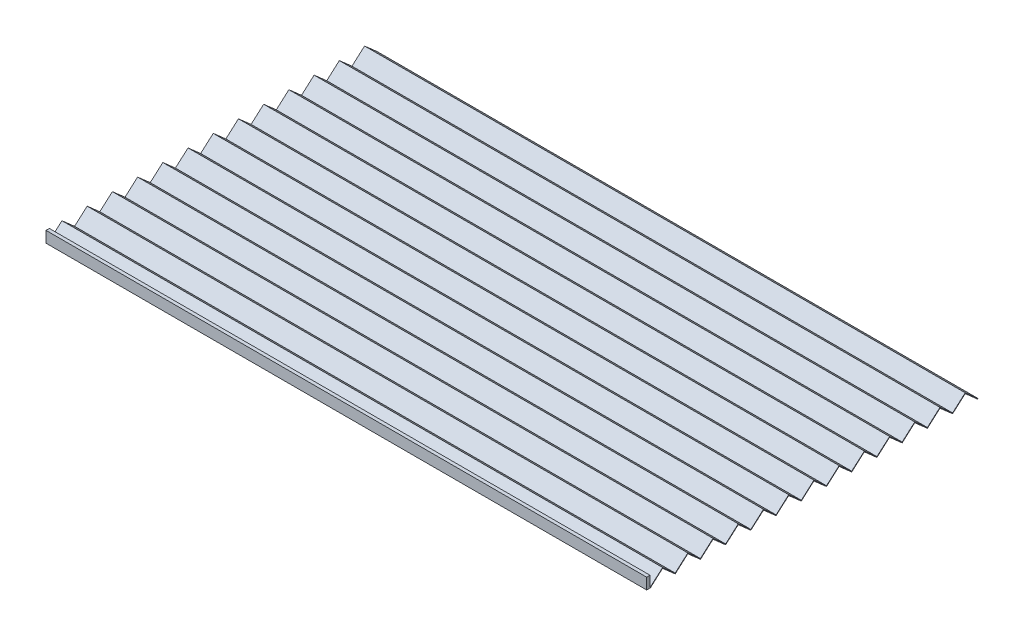
SolidWorks part; units mm, degrees
ref_plane "Front Plane" through (0, 0, 0) normal (0, 0, 1) x (1, 0, 0)
ref_plane "Top Plane" through (0, 0, 0) normal (0, 1, 0) x (1, 0, 0)
ref_plane "Right Plane" through (0, 0, 0) normal (1, 0, 0) x (0, 0, -1)
sketch "Sketch2" plane through (0, 0, 0) normal (0, 0, 1) x (1, 0, 0)
  line L1 (-270, 10) -> (270, 10)
  line L2 (-270, 10) -> (-270, 0)
  line L3 (-270, 0) -> (270, 0)
  line L4 (270, 10) -> (270, 0)
  point P4 (0, 0)
  dimension "D1" = 10
  dimension "D2" = 540
extrude "Boss-Extrude1" add sketch "Sketch2" along normal blind 3
sketch "Sketch3" plane through (270, 0, 0) normal (1, 0, 0) x (0, 0, -1)
  line L0 (0, 10) -> (294.7203, 10) construction
  line L1 (0, 0) -> (294.7203, 0) construction
  line L3 (0, 0) -> (11.3354, 10)
  line L4 (11.3354, 10) -> (22.6708, 0)
  line L5 (22.6708, 0) -> (34.0062, 10)
  line L6 (34.0062, 10) -> (45.3416, 0)
  line L7 (45.3416, 0) -> (56.677, 10)
  line L8 (56.677, 10) -> (68.0124, 0)
  line L9 (68.0124, 0) -> (79.3478, 10)
  line L10 (79.3478, 10) -> (90.6832, 0)
  line L11 (90.6832, 0) -> (102.0186, 10)
  line L12 (102.0186, 10) -> (113.354, 0)
  line L13 (113.354, 0) -> (124.6894, 10)
  line L14 (124.6894, 10) -> (136.0248, 0)
  line L15 (136.0248, 0) -> (147.3602, 10)
  line L16 (147.3602, 10) -> (158.6956, 0)
  line L17 (158.6956, 0) -> (170.031, 10)
  line L18 (170.031, 10) -> (181.3664, 0)
  line L20 (181.3664, 0) -> (192.7018, 10)
  line L21 (192.7018, 10) -> (204.0371, 0)
  line L22 (204.0371, 0) -> (215.3725, 10)
  line L23 (215.3725, 10) -> (226.7079, 0)
  line L24 (226.7079, 0) -> (238.0433, 10)
  line L25 (238.0433, 10) -> (249.3787, 0)
  line L26 (249.3787, 0) -> (260.7141, 10)
  line L27 (260.7141, 10) -> (272.0495, 0)
  line L28 (272.0495, 0) -> (283.3849, 10)
  line L29 (283.3849, 10) -> (294.7203, 0)
  line L30 (294.7203, 10) -> (294.7203, 0) construction
  line L32 (294.7203, 10) -> (294.7203, 0) construction
extrude "Extrude-Thin1" add sketch "Sketch3" against normal through all thin thin type mid plane wall 0.5
